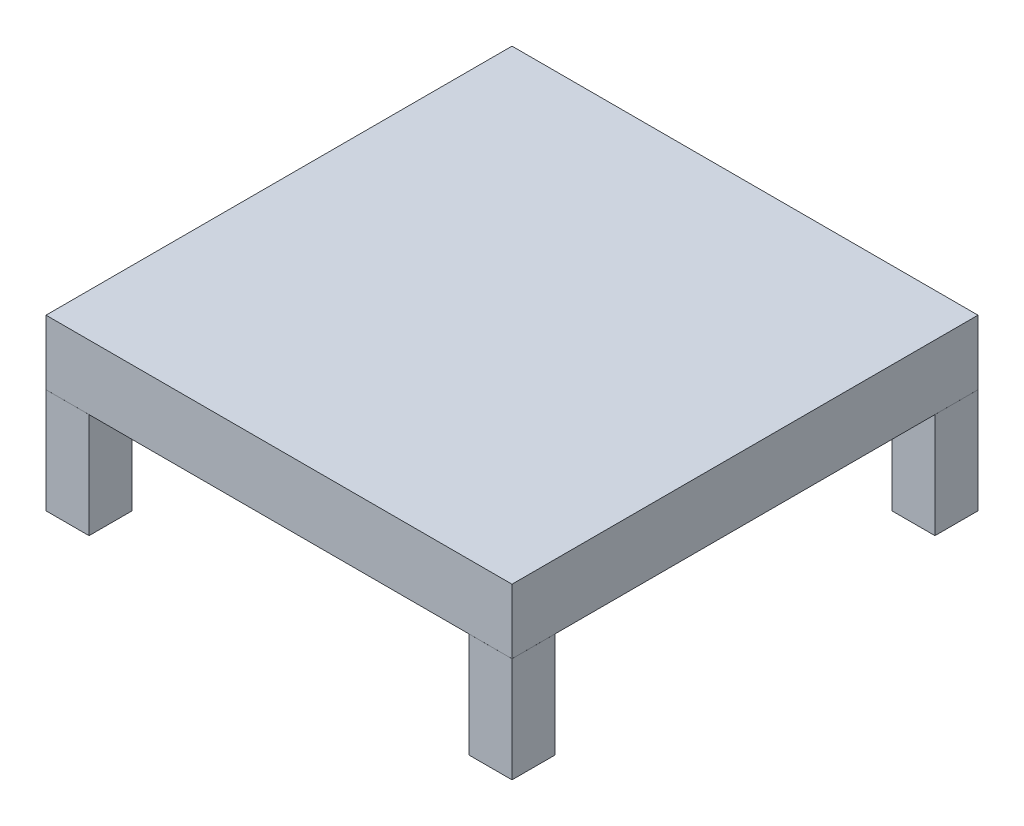
SolidWorks part; units mm, degrees
ref_plane "Front Plane" through (0, 0, 0) normal (0, 0, 1) x (1, 0, 0)
ref_plane "Top Plane" through (0, 0, 0) normal (0, 1, 0) x (1, 0, 0)
ref_plane "Right Plane" through (0, 0, 0) normal (1, 0, 0) x (0, 0, -1)
sketch "Sketch3" plane through (0, 0, 0) normal (0, 1, 0) x (1, 0, 0)
  line L0 (-275, 275) -> (275, -275) construction
  line L1 (-275, 275) -> (275, 275)
  line L2 (-275, 275) -> (-275, -275)
  line L3 (-275, -275) -> (275, -275)
  line L4 (275, 275) -> (275, -275)
  dimension "D1" = 550
extrude "Boss-Extrude2" add sketch "Sketch3" along normal mid plane 76.2
sketch "Sketch5" plane through (0, -38.1, 0) normal (0, -1, 0) x (1, 0, 0)
  line L0 (275, 0) -> (0, 0) construction
  line L1 (275, 275) -> (224.2, 275)
  line L2 (275, 275) -> (275, 224.2)
  line L3 (275, 224.2) -> (224.2, 224.2)
  line L4 (224.2, 275) -> (224.2, 224.2)
  line L5 (275, 275) -> (275, -275) construction
  line L6 (0, 0) -> (0, 275) construction
  line L7 (-275, 275) -> (275, 275) construction
  line L8 (224.2, -275) -> (224.2, -224.2)
  line L9 (275, -224.2) -> (224.2, -224.2)
  line L10 (275, -275) -> (275, -224.2)
  line L11 (275, -275) -> (224.2, -275)
  line L12 (-275, -275) -> (-224.2, -275)
  line L13 (-275, -275) -> (-275, -224.2)
  line L14 (-275, -224.2) -> (-224.2, -224.2)
  line L15 (-224.2, -275) -> (-224.2, -224.2)
  line L16 (-224.2, 275) -> (-224.2, 224.2)
  line L17 (-275, 224.2) -> (-224.2, 224.2)
  line L18 (-275, 275) -> (-275, 224.2)
  line L19 (-275, 275) -> (-224.2, 275)
  dimension "D1" = 50.8
extrude "Boss-Extrude3" add sketch "Sketch5" along normal offset from surface (373.8 mm away) 450 up to face at (0, 38.1, 0)
sketch "Sketch6" plane through (275, 0, 0) normal (1, 0, 0) x (0, 0, -1)
  line L1 (-295.1485, -38.1) -> (360.4823, -38.1)
  line L2 (-295.1485, -38.1) -> (-295.1485, -38.1254)
  line L3 (-295.1485, -38.1254) -> (360.4823, -38.1254)
  line L4 (360.4823, -38.1) -> (360.4823, -38.1254)
  dimension "D1" = 0.0254
extrude "Cut-Extrude1" cut sketch "Sketch6" against normal through all both and the other way through all
sketch "Sketch7" plane through (0, -411.9, 0) normal (0, -1, 0) x (1, 0, 0)
  line L1 (275, -275) -> (-275, -275)
  line L2 (275, -275) -> (275, 275)
  line L3 (275, 275) -> (-275, 275)
  line L4 (-275, -275) -> (-275, 275)
extrude "Cut-Extrude2" cut sketch "Sketch7" against normal offset from surface (249.975 mm away) 123.825 up to face at (0, -38.1, 0)
